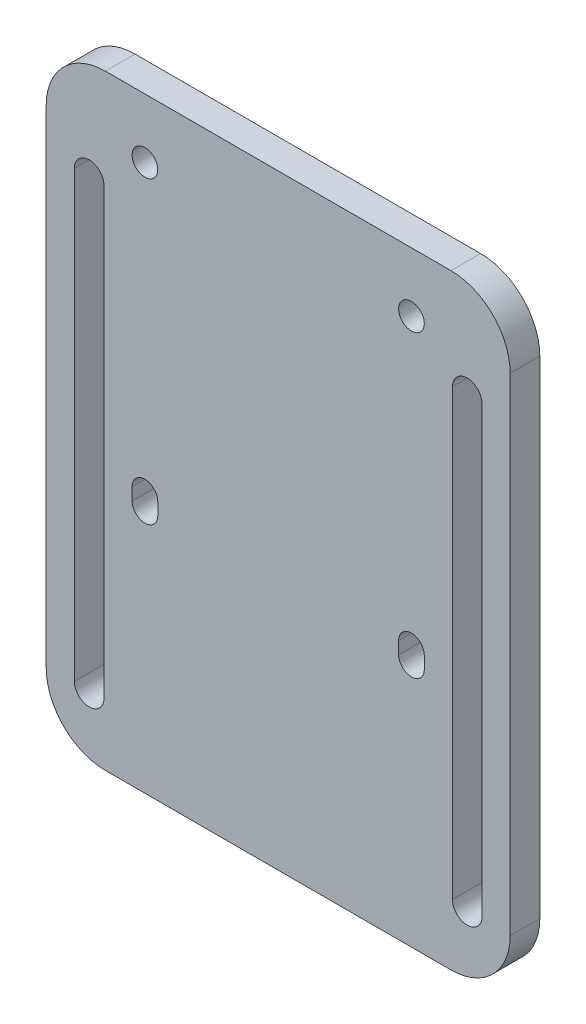
SolidWorks part; units mm, degrees
material "Polycarbonate (PC)"
ref_plane "Спереди" through (0, 0, 0) normal (0, 0, 1) x (1, 0, 0)
ref_plane "Сверху" through (0, 0, 0) normal (0, 1, 0) x (1, 0, 0)
ref_plane "Справа" through (0, 0, 0) normal (1, 0, 0) x (0, 0, -1)
sketch "Model" plane through (0, 0, 0) normal (0, 0, 1) x (1, 0, 0)
  line L0 (0, 130.393) -> (0, -19.607) construction
  line L1 (38.3, 119.0065) -> (38.3, 3.8567) construction
  line L2 (39.6393, 110.7) -> (20.3566, 110.7) construction
  line L3 (27, 114.3973) -> (27, 106.7903) construction
  line L8 (27, 57.0366) -> (27, 46.0463) construction
  line L14 (-27, 114.3973) -> (-27, 106.7903) construction
  line L15 (-39.6393, 110.7) -> (-20.3566, 110.7) construction
  line L16 (-29.6, 50) -> (-29.6, 52.5)
  line L17 (-29.6, 52.5) -> (-29.6, 50)
  line L18 (-27, 57.0366) -> (-27, 46.0463) construction
  line L19 (-24.4, 52.5) -> (-24.4, 50)
  line L20 (-24.4, 50) -> (-24.4, 52.5)
  line L22 (-41.3, 12.5) -> (-41.3, 102.5)
  line L23 (-41.3, 102.5) -> (-41.3, 12.5)
  line L24 (-38.3, 119.0065) -> (-38.3, 3.8567) construction
  line L25 (-35.3, 102.5) -> (-35.3, 12.5)
  line L26 (-35.3, 12.5) -> (-35.3, 102.5)
  line L29 (-41.3, 12.5) -> (-35.3, 12.5) construction
  line L2974 (29.6, 52.5) -> (29.6, 50)
  line L2987 (24.4, 50) -> (24.4, 52.5)
  line L2994 (35.3, 12.5) -> (35.3, 102.5)
  line L3007 (41.3, 102.5) -> (41.3, 12.5)
  line L3504 (35, 0) -> (-35, 0)
  line L3511 (-47, 12) -> (-47, 110.7)
  line L3518 (-35, 122.7) -> (35, 122.7)
  line L3525 (47, 110.7) -> (47, 12)
  line L3777 (24.4, 52.5) -> (24.4, 50)
  line L3790 (29.6, 50) -> (29.6, 52.5)
  line L3887 (41.3, 12.5) -> (41.3, 102.5)
  line L3900 (35.3, 102.5) -> (35.3, 12.5)
  arc A0 (-47, 12) -> (-35, 0) centre (-35, 12) ccw
  arc A1 (35, 0) -> (47, 12) centre (35, 12) ccw
  arc A2 (47, 110.7) -> (35, 122.7) centre (35, 110.7) ccw
  arc A3 (-47, 110.7) -> (-35, 122.7) centre (-35, 110.7) cw
  circle A8 centre (27, 110.7) radius 2.6
  arc A9 (24.4, 52.5) -> (29.6, 52.5) centre (27, 52.5) cw
  arc A10 (24.4, 50) -> (29.6, 50) centre (27, 50) ccw
  arc A11 (35.3, 12.5) -> (41.3, 12.5) centre (38.3, 12.5) ccw
  arc A12 (35.3, 102.5) -> (41.3, 102.5) centre (38.3, 102.5) cw
  arc A17 (-35.3, 102.5) -> (-41.3, 102.5) centre (-38.3, 102.5) ccw
  circle A18 centre (-27, 110.7) radius 2.6
  arc A19 (-24.4, 50) -> (-29.6, 50) centre (-27, 50) cw
  arc A20 (-24.4, 52.5) -> (-29.6, 52.5) centre (-27, 52.5) ccw
  arc A22 (-35.3, 12.5) -> (-41.3, 12.5) centre (-38.3, 12.5) cw
  point P22 (26.6472, 49.8151)
  dimension "D1" = 12
  dimension "D17" = 5.2
  dimension "D22" = 2.6
  dimension "D23" = 2.6
  dimension "D26" = 90
  dimension "D6" = 54
  dimension "D3" = 122.7
  dimension "D4" = 76.6
  dimension "D5" = 60.7
  dimension "D7" = 54
  dimension "D8" = 94
  dimension "D20" = 2.5
  dimension "D21" = 5.2
  dimension "D24" = 50
  dimension "D25" = 6
  dimension "D27" = 12.5
extrude "Base" add sketch "Model" along normal blind 6 contours A3 L3511 A0 L3504 A1 L3525 A2 L3518 L25 A22 L22 A17 A20 L19 A19 L16 L2994 A12 L3007 A11 A8 A10 L2987 A9 L2974 region at (0, 61.6424, 0)
